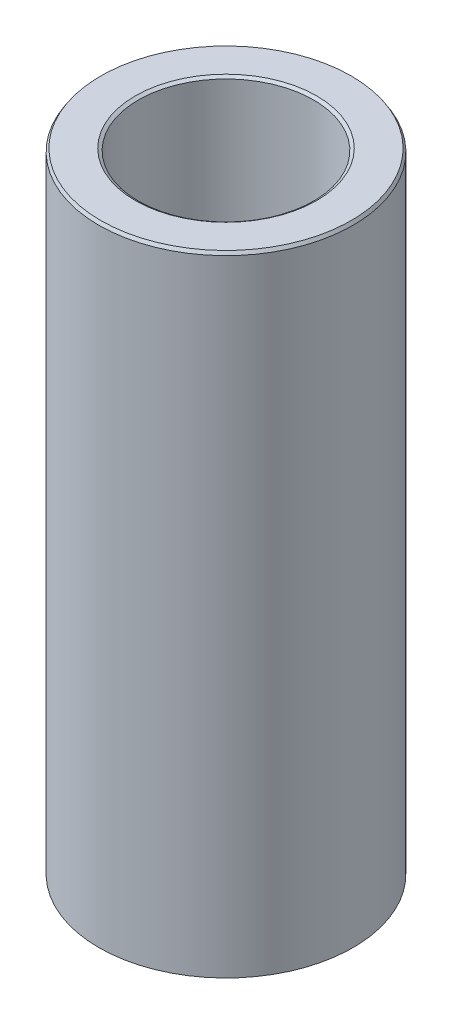
SolidWorks part; units mm, degrees
ref_plane "Front Plane" through (0, 0, 0) normal (0, 0, 1) x (1, 0, 0)
ref_plane "Top Plane" through (0, 0, 0) normal (0, 1, 0) x (1, 0, 0)
ref_plane "Right Plane" through (0, 0, 0) normal (1, 0, 0) x (0, 0, -1)
sketch "Sketch1" plane through (0, 0, 0) normal (0, 1, 0) x (1, 0, 0)
  circle A0 centre (0, 0) radius 55
  dimension "SLEEVE_OD" = 110
extrude "Boss-Extrude1" add sketch "Sketch1" along normal blind 272.6771
sketch "Sketch2" plane through (0, 0, 0) normal (0, 1, 0) x (1, 0, 0)
  circle A0 centre (0, 0) radius 37.8855
  dimension "BORE_D" = 75.7709
extrude "Cut-Extrude1" cut sketch "Sketch2" along normal through all
chamfer "Chamfer1" distance 1.3351 angle 32.511 4 edges at (0, 272.6771, 37.8855) (0, 0, 37.8855) (0, 0, 55) (0, 272.6771, 55) first distance on face at (0, 272.6771, 37.8855) first distance on face at (0, 0, 37.8855) first distance on face at (0, 272.6771, 55)
